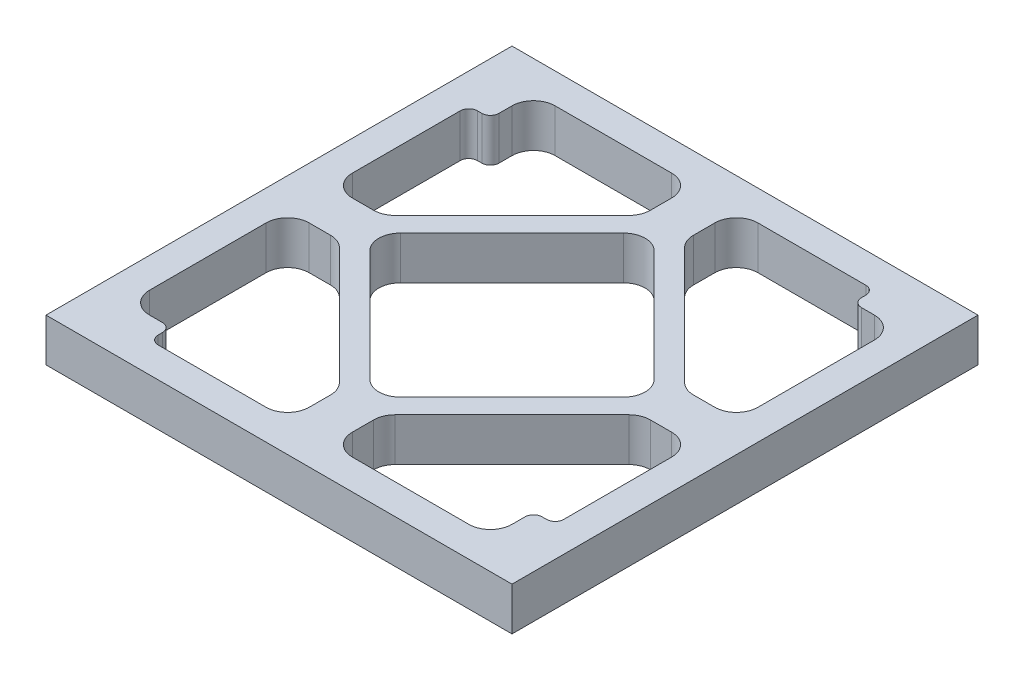
SolidWorks part; units mm, degrees
note: '?' marks a value the reader was unsure of.
material "6061-T6 (SS)"
ref_plane "Front Plane" through (0, 0, 0) normal (0, 0, 1) x (1, 0, 0)
ref_plane "Top Plane" through (0, 0, 0) normal (0, 1, 0) x (1, 0, 0)
ref_plane "Right Plane" through (0, 0, 0) normal (1, 0, 0) x (0, 0, -1)
sketch "Sketch1" plane through (0, 0, 0) normal (0, 1, 0) x (1, 0, 0)
  line L0 (-42, 47) -> (-42, 37)
  line L1 (-52, 52) -> (52, 52) construction
  line L2 (-52, 52) -> (-52, -52) construction
  line L3 (-52, -52) -> (52, -52) construction
  line L4 (52, 52) -> (52, -52) construction
  line L5 (-47, 5) -> (-35, 5)
  line L6 (-35, 5) -> (-5, 35)
  line L7 (-5, 35) -> (-5, 47)
  line L8 (-5, 47) -> (-42, 47)
  line L9 (0, 0) -> (0, 76.3292) construction
  line L10 (0, 0) -> (-78.8537, 0) construction
  line L11 (0, 0) -> (-66.7994, 66.7994) construction
  line L12 (-32.9289, 0) -> (0, 32.9289)
  line L13 (0, 32.9289) -> (32.9289, 0)
  line L14 (32.9289, 0) -> (0, -32.9289)
  line L15 (0, -32.9289) -> (-32.9289, 0)
  line L16 (5, 47) -> (5, 35)
  line L17 (37, 47) -> (5, 47)
  line L18 (37, 42) -> (37, 47)
  line L19 (47, 42) -> (37, 42)
  line L20 (47, 5) -> (47, 42)
  line L21 (35, 5) -> (47, 5)
  line L22 (5, 35) -> (35, 5)
  line L23 (47, -5) -> (35, -5)
  line L24 (47, -37) -> (47, -5)
  line L25 (42, -37) -> (47, -37)
  line L26 (42, -47) -> (42, -37)
  line L27 (5, -47) -> (42, -47)
  line L28 (5, -35) -> (5, -47)
  line L29 (35, -5) -> (5, -35)
  line L30 (-5, -47) -> (-5, -35)
  line L31 (-42, 37) -> (-47, 37)
  line L32 (-47, 37) -> (-47, 5)
  line L33 (-37, -47) -> (-5, -47)
  line L34 (-37, -42) -> (-37, -47)
  line L35 (-47, -42) -> (-37, -42)
  line L36 (-47, -5) -> (-47, -42)
  line L37 (-35, -5) -> (-47, -5)
  line L38 (-5, -35) -> (-35, -5)
  line L40 (-54, 54) -> (54, 54)
  line L41 (-54, 54) -> (-54, -54)
  line L42 (-54, -54) -> (54, -54)
  line L43 (54, 54) -> (54, -54)
  point P36 (0.1996, 0.1996)
  point P45 (0, 0)
  dimension "D1" = 104
  dimension "D2" = 5
  dimension "D3" = 5
  dimension "D4" = 5
  dimension "D5" = 5
  dimension "D6" = 5
  dimension "D7" = 12
  dimension "D8" = 10
  dimension "D9" = 10
  dimension "D11" = 2
  dimension "D12" = 2
  dimension "D13" = 2
  dimension "D10" = 4
extrude "Boss-Extrude1" add sketch "Sketch1" along normal blind 10
fillet "Fillet1" radius 5 24 edges at (32.9289, 5, 0) (0, 5, 32.9289) (-32.9289, 5, 0) (0, 5, -32.9289) (-5, 5, -47) (-5, 5, -35) (-35, 5, -5) (-47, 5, 42) (-47, 5, 5) (-35, 5, 5) (-5, 5, 35) (-5, 5, 47) (42, 5, 47) (47, 5, 5) (35, 5, 5) (5, 5, 35) (5, 5, 47) (47, 5, -42) (47, 5, -5) (35, 5, -5) (5, 5, -35) (5, 5, -47) (-42, 5, -47) (-47, 5, -5)
sketch "Sketch2" plane through (0, 10, 0) normal (0, 1, 0) x (1, 0, 0)
  line L0 (-52, 52) -> (-42, 52)
  line L1 (52, 52) -> (-52, 52) construction
  line L2 (-42, 52) -> (-42, 50)
  line L3 (-42, 50) -> (-50, 50)
  line L4 (-50, 50) -> (-50, 42)
  line L5 (-50, 42) -> (-52, 42)
  line L6 (-52, 52) -> (-52, -52) construction
  line L7 (-52, 42) -> (-52, 52)
  dimension "D1" = 2
  dimension "D2" = 10
extrude "Cut-Extrude1" [suppressed] cut sketch "Sketch2" against normal through all
ref_axis "Axis1" through (0, 10.5, 0) along (0, -1, 0)?
pattern_circular "CirPattern1" [suppressed] count 4 over 360 about axis through (0, 10.5, 0) along (0, -1, 0)
hole_wizard "CBORE for #6 Binding Head Machine Screw1" [suppressed] positions "Sketch3" profile "Sketch5" counterbore size "#6" standard "ANSI Inch"
sketch "Sketch3" plane through (0, 10, 0) normal (0, 1, 0) x (1, 0, 0)
  line L2 (0, 36) -> (36, 0)
  line L3 (-36, 0) -> (0, -36)
  line L4 (36, 0) -> (0, -36)
  line L6 (0, 0) -> (0, 48.9753) construction
  line L7 (0, 0) -> (-18.2924, 0) construction
  line L9 (-36, 0) -> (0, 36)
  line L11 (-3.5355, 29.3934) -> (-29.3934, 3.5355) construction
  point P0 (0, 36)
  point P199 (-36, 0)
  point P315 (0, -36)
  point P316 (36, 0)
  dimension "D1" = 36
sketch "Sketch5" plane through (0, 10, -36) normal (1, 0, 0) x (0, 0, 1)
  line L0 (0, 0) -> (0, 10)
  line L1 (0, 10) -> (1.8986, 10)
  line L3 (1.8986, 10) -> (1.8987, 2.2098)
  line L4 (1.8987, 2.2098) -> (3.9687, 2.2098)
  line L5 (3.9687, 2.2098) -> (3.9687, 0)
  line L7 (3.9687, 0) -> (0, 0)
  line L11 (0, -6.35) -> (0, 107.95) construction
  dimension "Thru Hole Dia." = 3.7973
  dimension "Thru Hole Depth" = 10
  dimension "C'Bore Dia." = 7.9375
  dimension "C'Bore Depth" = 2.2098
fillet "Fillet3" radius 2 8 edges at (-37, 5, 42) (-37, 5, 47) (42, 5, 37) (47, 5, 37) (37, 5, -42) (37, 5, -47) (-47, 5, -37) (-42, 5, -37)
hole_wizard "#6-32 Tapped Hole1" [suppressed] positions "Sketch6" profile "Sketch9" tap size "#6-32" standard "ANSI Inch"
sketch "Sketch6" [suppressed] plane through (50, 0, 0) normal (1, 0, 0) x (0, 0, -1)
  line L2 (42, 10) -> (52, 0)
  point P0 (47, 5)
  point P13 (47, 5)
sketch "Sketch9" plane through (50, 5, -47) normal (0, 1, 0) x (0, 0, -1)
  line L0 (0, 0) -> (0, 20.8127)
  line L1 (0, 20.8127) -> (1.3525, 20)
  line L2 (1.3525, 20) -> (1.3525, 0)
  line L5 (1.3525, 0) -> (0, 0)
  line L10 (0, 20.8127) -> (-1.3526, 20) construction
  line L11 (0, -6.35) -> (0, 107.95) construction
  dimension "Tap Drill Dia." = 2.7051
  dimension "Tap Drill Depth" = 20
  dimension "Drill Angle" = 118
cosmetic thread "Hole Thread1" [suppressed] parameters "D1"=7.01, "D2"=3.5052
pattern_circular "CirPattern5" [suppressed] count 4 over 360 about axis through (0, 10.5, 0) along (0, -1, 0)
